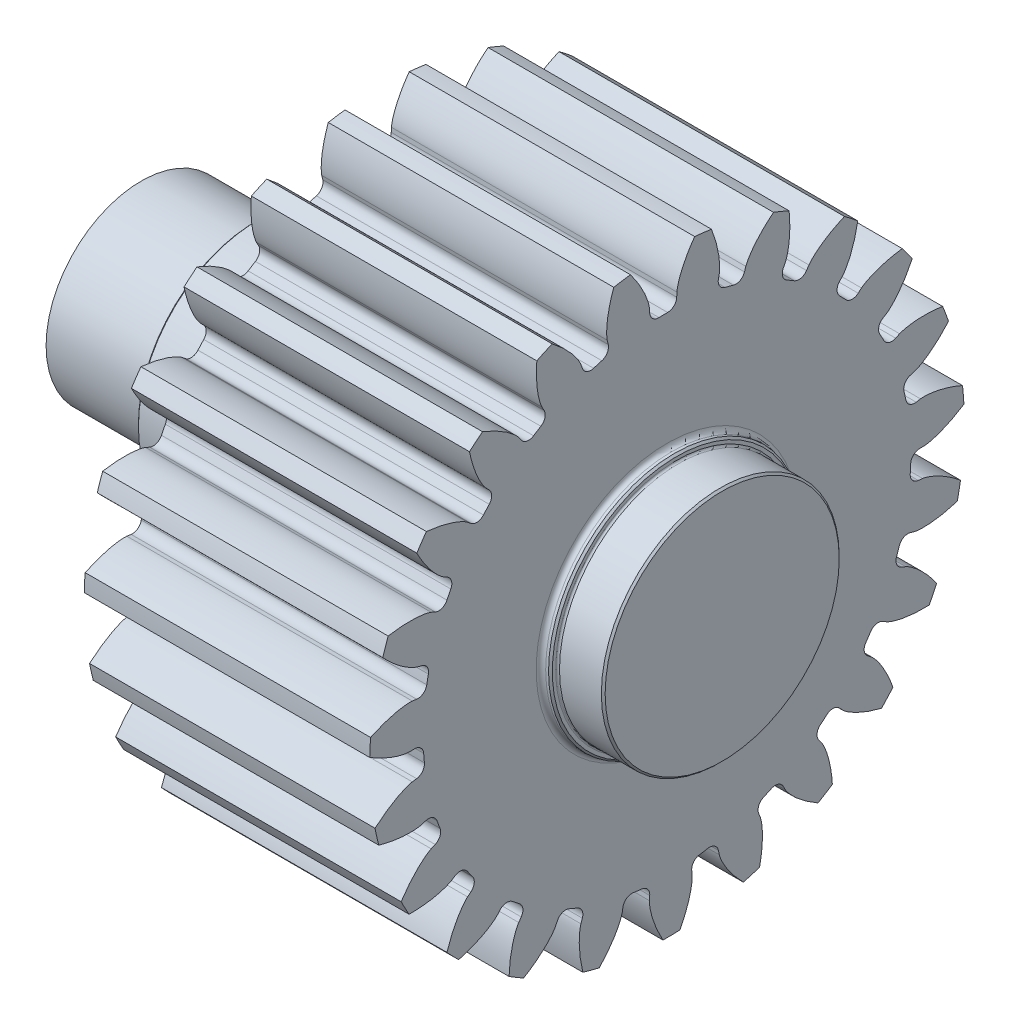
SolidWorks part; units mm, degrees
material "1.7225 (42CrMo4)"
ref_plane "前基準面" through (0, 0, 0) normal (0, 0, 1) x (1, 0, 0)
ref_plane "上基準面" through (0, 0, 0) normal (0, 1, 0) x (1, 0, 0)
ref_plane "右基準面" through (0, 0, 0) normal (1, 0, 0) x (0, 0, -1)
sketch "PitchDiameterRef" plane through (0, 0, 0) normal (1, 0, 0) x (0, 0, -1)
  circle A2 centre (0, 0) radius 28.75
  dimension "D1" = 57.5
sketch "ParametricInvoluteProfile" plane through (0, 0, 0) normal (1, 0, 0) x (0, 0, -1)
  spline S0 degree 4 poles (27.0162, 0) (27.0285, 0.0002) (27.063, 0.0014) (27.1283, 0.0062) (27.2345, 0.0176) (27.3694, 0.0372) (27.5431, 0.0686) (27.7467, 0.1133) (27.9692, 0.1703) (28.2097, 0.2409) (28.4481, 0.3188) (28.6843, 0.4035) (28.9181, 0.4941) (29.1993, 0.6113) (29.5336, 0.7619) (29.9198, 0.9526) (30.3521, 1.186) (30.786, 1.442) (31.2073, 1.7086) (31.6258, 1.9947) (32.0256, 2.2834) (32.4331, 2.5998) (32.8052, 2.9004) (33.2127, 3.2553) (33.5389, 3.547) (33.9586, 3.9505) (34.2034, 4.1944) (34.486, 4.4862) (34.6095, 4.6192) (34.6856, 4.701) knots 0 0 0 0 0 0.005377 0.015084 0.028532 0.04661 0.064855 0.092111 0.119476 0.146842 0.174209 0.201575 0.228941 0.256307 0.307035 0.361767 0.4165 0.471232 0.525964 0.580697 0.635429 0.690161 0.744894 0.799626 0.854358 0.909091 0.954545 1 1 1 1 1 construction
  spline S1 degree 4 poles (27.0162, 0) (27.0285, 0.0002) (27.063, 0.0014) (27.1283, 0.0062) (27.2345, 0.0176) (27.3694, 0.0372) (27.5431, 0.0686) (27.7467, 0.1133) (27.9692, 0.1703) (28.2097, 0.2409) (28.4481, 0.3188) (28.6843, 0.4035) (28.9181, 0.4941) (29.1993, 0.6113) (29.5336, 0.7619) (29.9198, 0.9526) (30.3521, 1.186) (30.786, 1.442) (31.2073, 1.7086) (31.6258, 1.9947) (32.0256, 2.2834) (32.4331, 2.5998) (32.8052, 2.9004) (33.2127, 3.2553) (33.5389, 3.547) (33.8676, 3.863) (34.0264, 4.019) (34.107, 4.0996) knots 0 0 0 0 0 0.005377 0.015084 0.028532 0.04661 0.064855 0.092111 0.119476 0.146842 0.174209 0.201575 0.228941 0.256307 0.307035 0.361767 0.4165 0.471232 0.525964 0.580697 0.635429 0.690161 0.744894 0.799626 0.854358 0.909091 0.909091 0.909091 0.909091 0.909091
sketch "Sketch4" plane through (0, 0, 0) normal (1, 0, 0) x (0, 0, -1)
  line L0 (0, 0) -> (22.0467, 0) construction
  line L1 (0, 0) -> (28.709, -1.5343) construction
  line L4 (27.0162, 0) -> (25.625, 0)
  line L5 (26.8623, -2.8794) -> (25.479, -2.7311)
  circle A4 centre (0, 0) radius 25.625
  circle A5 centre (0, 0) radius 27.0162
  arc A6 (28.709, -1.5343) -> (28.7468, 0.4285) centre (0, 0) ccw
  circle A7 centre (0, 0) radius 31.25
  spline S1 degree 4 poles (-12.4557, 2999.3672) (23.1098, 39.4632) (24.4791, 0.6167) (25.8797, -0.1273) (27.2345, 0.0176) (27.3694, 0.0372) (27.5431, 0.0686) (27.7467, 0.1133) (27.9692, 0.1703) (28.2097, 0.2409) (28.4481, 0.3188) (28.6843, 0.4035) (28.9181, 0.4941) (29.1993, 0.6113) (29.5336, 0.7619) (29.9198, 0.9526) (30.3521, 1.186) (30.786, 1.442) (31.2073, 1.7086) (31.6258, 1.9947) (32.0256, 2.2834) (32.4331, 2.5998) (32.8052, 2.9004) (33.2127, 3.2553) (34.8396, 4.7101) (39.7412, 9.974) (-23.2959, -52.3792) (2154.2897, 2126.1793) knots -0.547919 -0.547919 -0.547919 -0.547919 -0.547919 0.005377 0.015084 0.028532 0.04661 0.064855 0.092111 0.119476 0.146842 0.174209 0.201575 0.228941 0.256307 0.307035 0.361767 0.4165 0.471232 0.525964 0.580697 0.635429 0.690161 0.744894 0.799626 0.854358 1.782104 1.782104 1.782104 1.782104 1.782104 only from (27.0162, 0) to (34.107, 4.0996) construction
  spline S2 degree 4 poles (27.0162, 0) (27.0285, 0.0002) (27.063, 0.0014) (27.1283, 0.0062) (27.2345, 0.0176) (27.3694, 0.0372) (27.5431, 0.0686) (27.7467, 0.1133) (27.9692, 0.1703) (28.2097, 0.2409) (28.4481, 0.3188) (28.6843, 0.4035) (28.9181, 0.4941) (29.1993, 0.6113) (29.5336, 0.7619) (29.9198, 0.9526) (30.3521, 1.186) (30.786, 1.442) (31.2073, 1.7086) (31.6258, 1.9947) (32.0256, 2.2834) (32.4331, 2.5998) (32.8052, 2.9004) (33.2127, 3.2553) (33.5389, 3.547) (33.8676, 3.863) (34.0264, 4.019) (34.107, 4.0996) knots 0 0 0 0 0 0.005377 0.015084 0.028532 0.04661 0.064855 0.092111 0.119476 0.146842 0.174209 0.201575 0.228941 0.256307 0.307035 0.361767 0.4165 0.471232 0.525964 0.580697 0.635429 0.690161 0.744894 0.799626 0.854358 0.909091 0.909091 0.909091 0.909091 0.909091
  spline S4 degree 4 poles (26.8623, -2.8794) (26.8745, -2.8809) (26.9087, -2.8858) (26.9731, -2.8975) (27.0775, -2.9201) (27.2095, -2.954) (27.3789, -3.0038) (27.5766, -3.0698) (27.7918, -3.1503) (28.0234, -3.2461) (28.2521, -3.349) (28.478, -3.4584) (28.7007, -3.5734) (28.9678, -3.7198) (29.2842, -3.9052) (29.6479, -4.136) (30.0528, -4.4142) (30.457, -4.7149) (30.8474, -5.025) (31.233, -5.354) (31.5999, -5.6836) (31.9713, -6.0417) (32.3092, -6.3803) (32.6766, -6.7765) (32.9698, -7.1013) (33.263, -7.4506) (33.4042, -7.6226) (33.4758, -7.7114) knots 0 0 0 0 0 0.005377 0.015084 0.028532 0.04661 0.064855 0.092111 0.119476 0.146842 0.174209 0.201575 0.228941 0.256307 0.307035 0.361767 0.4165 0.471232 0.525964 0.580697 0.635429 0.690161 0.744894 0.799626 0.854358 0.909091 0.909091 0.909091 0.909091 0.909091
  dimension "D1" = 62.5
  dimension "D2" = 57.5
  dimension "D3" = 54.0323
  dimension "D4" = 51.25
  dimension "D5" = 1.9635
sketch "Sketch5" plane through (0, 0, 0) normal (1, 0, 0) x (0, 0, -1)
  circle A2 centre (0, 0) radius 31.25 construction
  circle A3 centre (0, 0) radius 31.25
extrude "Boss-Extrude1" add sketch "Sketch5" along normal blind 30
sketch "Sketch8" plane through (30, 0, 0) normal (1, 0, 0) x (0, 0, -1)
  line L0 (27.0162, 0) -> (25.625, 0) construction
  line L1 (26.8623, -2.8794) -> (25.479, -2.7311) construction
  line L2 (27.0162, 0) -> (25.625, 0)
  line L3 (26.8623, -2.8794) -> (25.479, -2.7311)
  circle A0 centre (0, 0) radius 25.625 construction
  circle A1 centre (0, 0) radius 31.25 construction
  arc A2 (25.479, -2.7311) -> (25.625, 0) centre (0, 0) ccw
  arc A3 (30.8431, -5.0262) -> (31.2032, 1.7104) centre (0, 0) ccw
  spline S0 degree 4 poles (11.8595, 999.8403) (24.091, 17.6208) (25.1288, 0.3173) (26.1866, -0.0945) (27.2345, 0.0176) (27.3694, 0.0372) (27.5431, 0.0686) (27.7467, 0.1133) (27.9692, 0.1703) (28.2097, 0.2409) (28.4481, 0.3188) (28.6843, 0.4035) (28.9181, 0.4941) (29.1993, 0.6113) (29.5336, 0.7619) (29.9198, 0.9526) (30.3521, 1.186) (30.786, 1.442) (31.2073, 1.7086) (31.6258, 1.9947) (32.0256, 2.2834) (32.4331, 2.5998) (32.8052, 2.9004) (33.2127, 3.2553) (34.5162, 4.4209) (37.837, 7.9411) (9.3324, -20.1528) (740.6444, 711.7303) knots -0.413254 -0.413254 -0.413254 -0.413254 -0.413254 0.005377 0.015084 0.028532 0.04661 0.064855 0.092111 0.119476 0.146842 0.174209 0.201575 0.228941 0.256307 0.307035 0.361767 0.4165 0.471232 0.525964 0.580697 0.635429 0.690161 0.744894 0.799626 0.854358 1.565081 1.565081 1.565081 1.565081 1.565081 only from (27.0162, 0) to (26.1486, 3.4643) construction
  spline S1 degree 4 poles (-94.7704, -995.4094) (22.0758, -20.088) (24.9518, -2.9937) (26.0475, -2.697) (27.0775, -2.9201) (27.2095, -2.954) (27.3789, -3.0038) (27.5766, -3.0698) (27.7918, -3.1503) (28.0234, -3.2461) (28.2521, -3.349) (28.478, -3.4584) (28.7007, -3.5734) (28.9678, -3.7198) (29.2842, -3.9052) (29.6479, -4.136) (30.0528, -4.4142) (30.457, -4.7149) (30.8474, -5.025) (31.233, -5.354) (31.5999, -5.6836) (31.9713, -6.0417) (32.3092, -6.3803) (32.6766, -6.7765) (33.8485, -8.0745) (36.7751, -11.9285) (11.4271, 19.0434) (660.5701, -786.6138) knots -0.413254 -0.413254 -0.413254 -0.413254 -0.413254 0.005377 0.015084 0.028532 0.04661 0.064855 0.092111 0.119476 0.146842 0.174209 0.201575 0.228941 0.256307 0.307035 0.361767 0.4165 0.471232 0.525964 0.580697 0.635429 0.690161 0.744894 0.799626 0.854358 1.565081 1.565081 1.565081 1.565081 1.565081 only from (26.8623, -2.8794) to (25.6305, -6.2315) construction
  spline S2 degree 4 poles (27.0162, 0) (27.0285, 0.0002) (27.063, 0.0014) (27.1283, 0.0062) (27.2345, 0.0176) (27.3694, 0.0372) (27.5431, 0.0686) (27.7467, 0.1133) (27.9692, 0.1703) (28.2097, 0.2409) (28.4481, 0.3188) (28.6843, 0.4035) (28.9181, 0.4941) (29.1993, 0.6113) (29.5336, 0.7619) (29.9198, 0.9526) (30.3521, 1.186) (30.7309, 1.4095) (30.9946, 1.5745) (31.1515, 1.6764) (31.2032, 1.7104) knots 0 0 0 0 0 0.005377 0.015084 0.028532 0.04661 0.064855 0.092111 0.119476 0.146842 0.174209 0.201575 0.228941 0.256307 0.307035 0.361767 0.4165 0.471232 0.498148 0.498148 0.498148 0.498148 0.498148
  spline S3 degree 4 poles (26.8623, -2.8794) (26.8745, -2.8809) (26.9087, -2.8858) (26.9731, -2.8975) (27.0775, -2.9201) (27.2095, -2.954) (27.3789, -3.0038) (27.5766, -3.0698) (27.7918, -3.1503) (28.0234, -3.2461) (28.2521, -3.349) (28.478, -3.4584) (28.7007, -3.5734) (28.9678, -3.7198) (29.2842, -3.9052) (29.6479, -4.136) (30.0528, -4.4142) (30.4056, -4.6767) (30.6503, -4.8689) (30.7954, -4.987) (30.8431, -5.0262) knots 0 0 0 0 0 0.005377 0.015084 0.028532 0.04661 0.064855 0.092111 0.119476 0.146842 0.174209 0.201575 0.228941 0.256307 0.307035 0.361767 0.4165 0.471232 0.498148 0.498148 0.498148 0.498148 0.498148
extrude "Cut-Extrude2" cut sketch "Sketch8" against normal up to surface (30 mm away) up to face at (0, 0, -31.25)
fillet "Fillet2" radius 0.95 2 edges at (15, -2.7311, -25.479) (15, 0, -25.625)
pattern_circular "CirPattern3" count 23 over 360 about axis through (30, 0, 0) along (-1, 0, 0) of "Cut-Extrude2", "Fillet2"
ref_axis "centerAxis" through (30, 0, 0) along (-1, 0, 0)
ref_plane "Plane1" through (-13.25, 0, 0) normal (-1, 0, 0) x (0, 0, 1)
sketch "Sketch12" plane through (0, 0, 0) normal (1, 0, 0) x (0, 0, -1)
  circle A0 centre (0, 0) radius 13.25
  dimension "D1" = 26.5
extrude "Boss-Extrude4" add sketch "Sketch12" against normal blind 1
sketch "Sketch10" plane through (-13.25, 0, 0) normal (-1, 0, 0) x (0, 0, 1)
  circle A0 centre (0, 0) radius 20
  circle A1 centre (0, 0) radius 12.5
  dimension "D1" = 40
  dimension "D2" = 25
extrude "Boss-Extrude2" add sketch "Sketch10" against normal up to body separate body contours A1 region at (-13.25, 0, 0)
sketch "Sketch11" plane through (0, 0, 0) normal (1, 0, 0) x (0, 0, -1)
  circle A0 centre (0, 0) radius 10
  dimension "D1" = 20
extrude "Boss-Extrude3" add sketch "Sketch11" against normal blind 12 from surface starting at face at (-13.25, 0, 12.5)
fillet "bearingHouseFillet" radius 0.2 1 edges at (-1, 0, -12.5)
chamfer "Chamfer1" distance 0.2 angle 45 1 edges at (-13.25, 0, 12.5)
fillet "Fillet4" radius 0.5 1 edges at (0, 0, -13.25)
sketch "Sketch14" plane through (-13.25, 0, 0) normal (-1, 0, 0) x (0, 0, 1)
  circle A0 centre (0, 0) radius 12.5
  circle A1 centre (0, 0) radius 13.25
  dimension "D1" = 25
  dimension "D2" = 26.5
extrude "Boss-Extrude5" add sketch "Sketch14" against normal blind 5.8 from surface contours A0 region at (-13.25, 0, 0) starting at face at (30, 0, 0)
extrude "Boss-Extrude6" add sketch "Sketch14<3>" against normal blind 1 from surface starting at face at (30, 0, -12.5)
sketch "Sketch14<3>" plane through (-13.25, 0, 0) normal (-1, 0, 0) x (0, 0, 1) same geometry as "Sketch14"
chamfer "Chamfer2" distance 0.2 angle 45 2 edges at (35.8, 0, -12.5) (31, 0, -13.25)
fillet "Fillet5" radius 0.2 1 edges at (31, 0, -12.5)
fillet "Fillet6" radius 0.5 1 edges at (30, 0, -13.25)
sketch "Sketch16" [suppressed] plane through (0, 0, 0) normal (0, 1, 0) x (1, 0, 0)
  line L0 (-25.25, 10) -> (-25.25, -10) construction
  line L6 (0, 0) -> (-25.25, 0) construction
  line L7 (-13.25, 11) -> (-13.25, -11) construction
  line L8 (-25.25, 2) -> (-13.25, 2)
  line L9 (-25.25, 2) -> (-25.25, 7)
  line L10 (-25.25, 7) -> (-13.25, 7)
  line L11 (-13.25, 2) -> (-13.25, 7)
  line L12 (-13.25, -2) -> (-13.25, -7)
  line L13 (-25.25, -7) -> (-13.25, -7)
  line L14 (-25.25, -2) -> (-25.25, -7)
  line L15 (-25.25, -2) -> (-13.25, -2)
  arc A0 (-13.25, 2) -> (-13.25, 7) centre (-13.25, 4.5) ccw
  arc A1 (-13.25, -2) -> (-13.25, -7) centre (-13.25, -4.5) cw
  dimension "D1" = 4
  dimension "D2" = 5
sketch "Sketch17" [suppressed] plane through (0, 0, 0) normal (1, 0, 0) x (0, 0, -1)
  line L0 (2, 9.798) -> (2, 7.448)
  line L2 (0, 0) -> (0, 10) construction
  circle A0 centre (0, 0) radius 10
  dimension "D1" = 20
  dimension "D2" = 4
  dimension "D3" = 2.35
extrude "Cut-Extrude3" [suppressed] cut sketch "Sketch16" along normal blind 5 from vertex contours L8 L11 L10 L9 | L11 A0 | L15 L14 L13 L12 | A1 L12 starting at point (0, 7.448, -2)
pattern_circular "CirPattern4" [suppressed] count 6 over 360 about axis through (30, 0, 0) along (-1, 0, 0) of bodies 114
ref_plane "Plane2" [suppressed] through (0, 0, 0) normal (0, 0.866, 0.5) x (-1, 0, 0)
sketch "Sketch18" [suppressed] plane through (0, 0, 0) normal (0, 0.866, 0.5) x (-1, 0, 0)
  line L0 (0, 0) -> (25.25, 0) construction
  line L1 (25.25, 1.9919) -> (25.25, 0) construction
  line L2 (25.25, 2) -> (13.25, 2)
  line L3 (25.25, 2) -> (25.25, -2)
  line L4 (25.25, -2) -> (13.25, -2)
  line L5 (13.25, 2) -> (13.25, -2)
  line L8 (13.25, 3.6763) -> (13.25, 1.9919) construction
  arc A0 (13.25, 2) -> (13.25, -2) centre (13.25, 0) ccw
  dimension "D1" = 4
extrude "Cut-Extrude4" [suppressed] cut sketch "Sketch18" along normal blind 5 from offset 7.91 contours L5 L0 L3 L2 | L0 L5 L4 L3 | L0 A0 L5 | A0 L0 L5
pattern_circular "CirPattern5" [suppressed] count 6 over 360 about axis through (30, 0, 0) along (-1, 0, 0) of bodies 116
equation "\"a\"= 20"
equation "\"M\"= 2.5"
equation "\"T\"= 23"
equation "\"R\"= 0.38 * \"M\""
equation "\"D\"= \"M\" * \"T\""
equation "\"Da\"= ( \"T\" + 2 ) * \"M\""
equation "\"Df\"= ( \"T\" - 2.5 ) * \"M\""
equation "\"Db\"= \"M\" * \"T\" * cos ( \"a\" )"
equation "\"rb\"= \"Db\" / 2"
equation "\"S\"= pi * \"M\" * 0.5"
equation "\"D1@Sketch4\"=\"Da\""
equation "\"D2@Sketch4\"=\"D\""
equation "\"D3@Sketch4\"=\"Db\""
equation "\"D4@Sketch4\"=\"Df\""
equation "\"D5@Sketch4\"=\"S\"/2"
equation "\"D1@Fillet2\"=\"R\""
equation "\"D1@CirPattern3\"=\"T\""
equation "\"input_a\"= 37.5"
equation "\"input_M\"= 1"
equation "\"input_T\"= 20"
equation "\"input_R\"= 0.38 * \"input_M\""
equation "\"input_D\"= \"input_M\" * \"input_T\""
equation "\"input_Df\"= ( \"input_T\" - 2.5 ) * \"input_M\""
equation "\"input_Db\"= \"input_M\" * \"input_T\" * cos ( \"input_a\" )"
equation "\"input_S\"= pi * \"input_M\" * 0.5"
equation "\"D1@PitchDiameterRef\"=\"D\""
